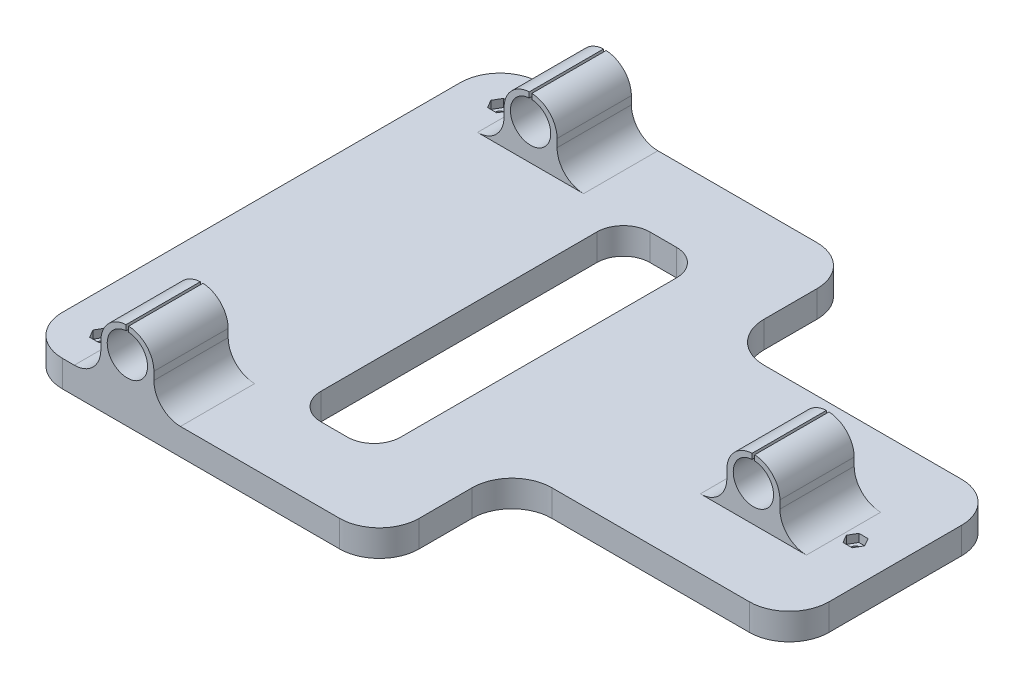
SolidWorks part; units mm, degrees
ref_plane "Front Plane" through (0, 0, 0) normal (0, 0, 1) x (1, 0, 0)
ref_plane "Top Plane" through (0, 0, 0) normal (0, 1, 0) x (1, 0, 0)
ref_plane "Right Plane" through (0, 0, 0) normal (1, 0, 0) x (0, 0, -1)
sketch "Sketch1" plane through (0, 0, 0) normal (0, 1, 0) x (1, 0, 0)
  line L0 (-104.5, 75) -> (-104.5, -75) construction
  line L1 (-104.5, 0) -> (0, 0) construction
  line L2 (0, 0) -> (104.5, 0) construction
  line L4 (-119.5, -90) -> (119.5, -90)
  line L5 (-119.5, -90) -> (-119.5, 90)
  line L6 (-119.5, 90) -> (119.5, 90)
  line L7 (119.5, -90) -> (119.5, 90)
  line L8 (-119.5, -90) -> (119.5, 90) construction
  line L9 (-119.5, 90) -> (119.5, -90) construction
  circle A0 centre (104.5, 0) radius 1.75
  circle A1 centre (-104.5, 75) radius 1.75
  circle A2 centre (-104.5, -75) radius 1.75
  dimension "D2" = 3.5
  dimension "D4" = 15
  dimension "D5" = 15
  dimension "D1" = 209
  dimension "D3" = 150
extrude "Boss-Extrude1" add sketch "Sketch1" along normal blind 10
sketch "Sketch2" plane through (0, 10, 0) normal (0, 1, 0) x (1, 0, 0)
  line L0 (-80, 90) -> (-80, -90) construction
  line L1 (119.5, 90) -> (-119.5, 90) construction
  line L2 (-119.5, -90) -> (119.5, -90) construction
  line L3 (80, 90) -> (80, -90) construction
  line L5 (-90, 90) -> (-70, 90)
  line L6 (-90, 90) -> (-90, 62)
  line L7 (-90, 62) -> (-70, 62)
  line L8 (-70, 90) -> (-70, 62)
  line L9 (-90, 90) -> (-70, 62) construction
  line L10 (-90, 62) -> (-70, 90) construction
  line L11 (-90, -62) -> (-70, -62)
  line L12 (-90, -62) -> (-90, -90)
  line L13 (-90, -90) -> (-70, -90)
  line L14 (-70, -62) -> (-70, -90)
  line L15 (-90, -62) -> (-70, -90) construction
  line L16 (-90, -90) -> (-70, -62) construction
  line L17 (90, 14) -> (70, 14)
  line L18 (90, 14) -> (90, -14)
  line L19 (90, -14) -> (70, -14)
  line L20 (70, 14) -> (70, -14)
  line L21 (90, 14) -> (70, -14) construction
  line L22 (90, -14) -> (70, 14) construction
  point P8 (-80, 76)
  point P14 (-80, -76)
  point P19 (80, 0)
  dimension "D1" = 80
  dimension "D2" = 80
  dimension "D3" = 20
  dimension "D4" = 28
extrude "Boss-Extrude2" add sketch "Sketch2" along normal blind 23
sketch "Sketch3" plane through (0, 0, -90) normal (0, 0, -1) x (-1, 0, 0)
  line L0 (70, 33) -> (90, 33) construction
  circle A0 centre (80, 23.4) radius 7.6
  point P4 (80, 33)
  dimension "D1" = 15.2
  dimension "D2" = 9.6
extrude "Cut-Extrude1" cut sketch "Sketch3" against normal through all both and the other way through all
fillet "Fillet1" radius 10 6 edges at (90, 33, 0) (70, 33, 0) (-90, 33, 76) (-70, 33, 76) (-70, 33, -76) (-90, 33, -76)
mirror "Mirror1" about plane through (0, 0, 0) normal (1, 0, 0) of "Cut-Extrude1"
fillet "Fillet2" radius 10 6 edges at (70, 10, 0) (90, 10, 0) (-70, 10, 76) (-90, 10, 76) (-70, 10, -76) (-90, 10, -76)
sketch "Sketch4" plane through (0, 10, 0) normal (0, 1, 0) x (1, 0, 0)
  line L0 (0, 0) -> (-30, 0) construction
  line L1 (-100, 62) -> (-60, 62) construction
  line L2 (-35, 62) -> (-25, 62)
  line L3 (-45, 52) -> (-45, -52)
  line L4 (-35, -62) -> (-25, -62)
  line L5 (-15, 52) -> (-15, -52)
  line L6 (-45, 62) -> (-15, -62) construction
  line L7 (-45, -62) -> (-15, 62) construction
  arc A0 (-45, -52) -> (-35, -62) centre (-35, -52) ccw
  arc A1 (-25, -62) -> (-15, -52) centre (-25, -52) ccw
  arc A2 (-25, 62) -> (-15, 52) centre (-25, 52) cw
  arc A3 (-35, 62) -> (-45, 52) centre (-35, 52) ccw
  dimension "D3" = 10
  dimension "D1" = 30
  dimension "D2" = 30
extrude "Cut-Extrude2" cut sketch "Sketch4" against normal blind 20
sketch "Sketch5" plane through (0, 10, 0) normal (0, 1, 0) x (1, 0, 0)
  line L0 (119.5, 40) -> (15, 40)
  line L1 (119.5, -90) -> (119.5, 90) construction
  line L2 (15, 40) -> (15, 90)
  line L3 (119.5, 90) -> (-60, 90) construction
  line L4 (15, 90) -> (119.5, 90)
  line L5 (119.5, 90) -> (119.5, 40)
  line L6 (-15, -52) -> (-15, 52) construction
  dimension "D1" = 50
  dimension "D2" = 30
extrude "Cut-Extrude3" cut sketch "Sketch5" against normal blind 20
fillet "Fillet3" radius 15 4 edges at (-119.5, 5, -90) (119.5, 5, -40) (15, 5, -40) (15, 5, -90)
mirror "Mirror2" about plane through (0, 0, 0) normal (0, 0, 1) of "Cut-Extrude3"
fillet "Fillet4" radius 15 4 edges at (119.5, 5, 40) (15, 5, 40) (15, 5, 90) (-119.5, 5, 90)
sketch "Sketch6" plane through (0, 10, 0) normal (0, 1, 0) x (1, 0, 0)
  line L1 (-107.9641, -75) -> (-106.2321, -78)
  line L2 (-106.2321, -78) -> (-102.7679, -78)
  line L3 (-102.7679, -78) -> (-101.0359, -75)
  line L4 (-101.0359, -75) -> (-102.7679, -72)
  line L5 (-102.7679, -72) -> (-106.2321, -72)
  line L6 (-106.2321, -72) -> (-107.9641, -75)
  line L7 (-107.9641, 75) -> (-106.2321, 72)
  line L8 (-106.2321, 72) -> (-102.7679, 72)
  line L9 (-102.7679, 72) -> (-101.0359, 75)
  line L10 (-101.0359, 75) -> (-102.7679, 78)
  line L11 (-102.7679, 78) -> (-106.2321, 78)
  line L12 (-106.2321, 78) -> (-107.9641, 75)
  line L13 (107.9641, 0) -> (106.2321, 3)
  line L14 (106.2321, 3) -> (102.7679, 3)
  line L15 (102.7679, 3) -> (101.0359, 0)
  line L16 (101.0359, 0) -> (102.7679, -3)
  line L17 (102.7679, -3) -> (106.2321, -3)
  line L18 (106.2321, -3) -> (107.9641, 0)
  circle A0 centre (-104.5, -75) radius 3 construction
  circle A1 centre (-104.5, 75) radius 3 construction
  circle A2 centre (104.5, 0) radius 3 construction
  dimension "D1" = 6
extrude "Cut-Extrude4" cut sketch "Sketch6" against normal blind 3
ref_plane "Plane1" through (0, 25, 0) normal (0, 1, 0) x (1, 0, 0)
sketch "Sketch7" plane through (0, 25, 0) normal (0, 1, 0) x (1, 0, 0)
  line L12 (-86.0498, 90) -> (-73.9502, 90) construction
  line L13 (73.9502, 14) -> (86.0498, 14) construction
  line L14 (-86.0498, -62) -> (-73.9502, -62) construction
  line L15 (-80, -62) -> (-80, -97.181)
  line L16 (-80, 90) -> (-80, 59.3608)
  line L17 (80, 14) -> (80, -17.2271)
extrude "Cut-Extrude-Thin1" cut sketch "Sketch7" along normal blind 21 thin thin type mid plane wall 1
